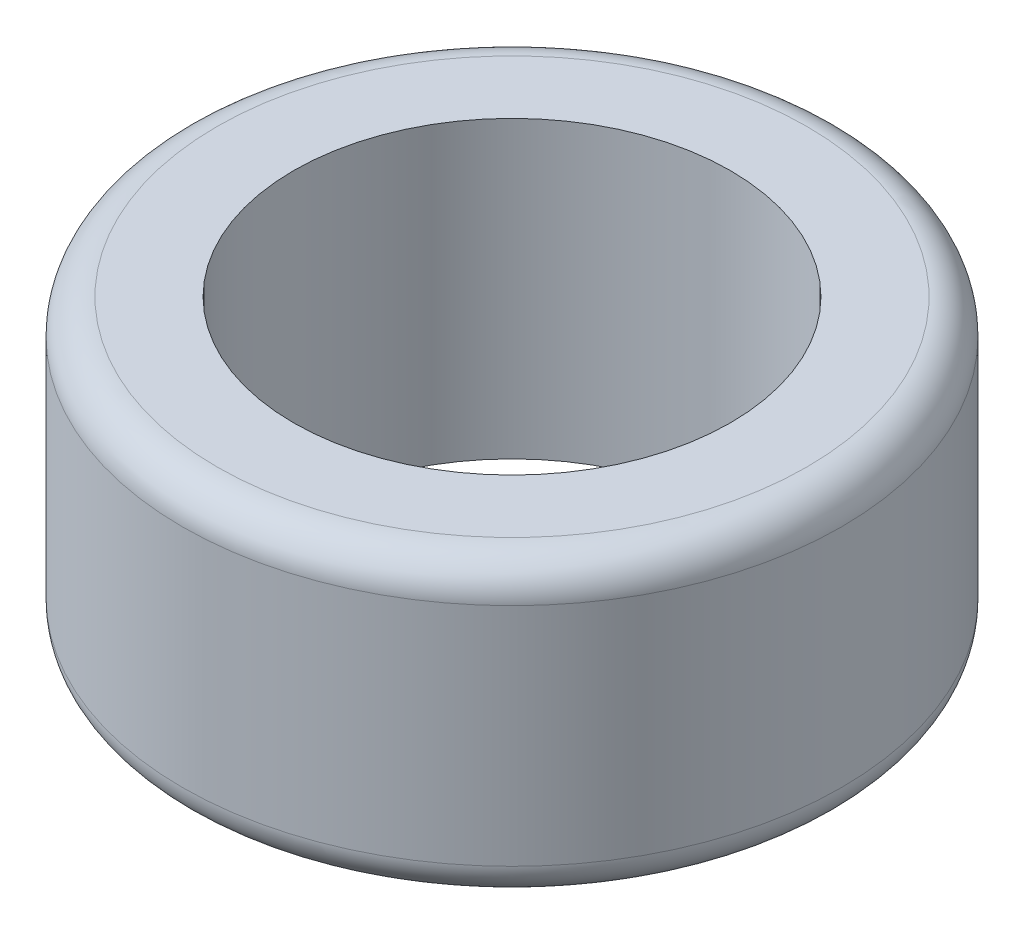
SolidWorks part; units mm, degrees
ref_plane "Front Plane" through (0, 0, 0) normal (0, 0, 1) x (1, 0, 0)
ref_plane "Top Plane" through (0, 0, 0) normal (0, 1, 0) x (1, 0, 0)
ref_plane "Right Plane" through (0, 0, 0) normal (1, 0, 0) x (0, 0, -1)
sketch "Sketch4" plane through (0, 0, 0) normal (0, 0, 1) x (1, 0, 0)
  line L0 (-152.4, 0) -> (-152.4, 205.74)
  line L1 (-152.4, 205.74) -> (-205.74, 205.74)
  line L2 (-152.4, 0) -> (-205.74, 0)
  line L3 (-229.87, 181.61) -> (-229.87, 24.13)
  line L4 (-152.4, 102.87) -> (-204.0709, 102.87) construction
  line L5 (0, 0) -> (0, 160.7909) construction
  arc A0 (-205.74, 205.74) -> (-229.87, 181.61) centre (-205.74, 181.61) ccw
  arc A1 (-229.87, 24.13) -> (-205.74, 0) centre (-205.74, 24.13) ccw
  point P11 (-229.87, 102.87)
  point P14 (-177.8439, 0)
  point P15 (-200.9466, 0)
  dimension "D1" = 205.74
  dimension "D2" = 157.48
  dimension "D3" = 229.87
  dimension "D4" = 152.4
revolve "Revolve1" add sketch "Sketch4" angle 360 about L5
